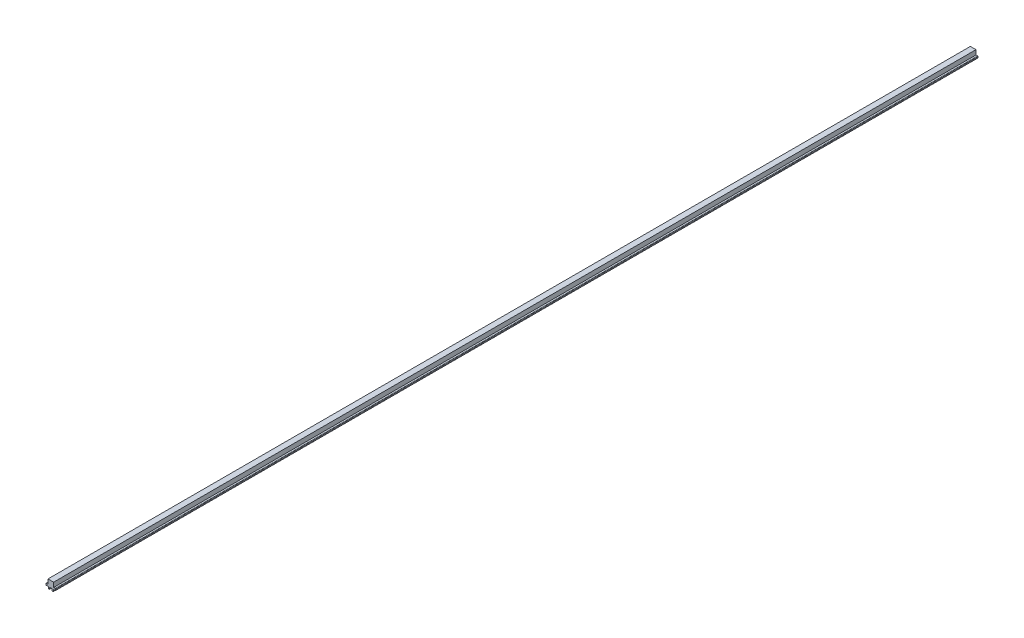
SolidWorks part; units mm, degrees
ref_plane "Front Plane" through (0, 0, 0) normal (0, 0, 1) x (1, 0, 0)
ref_plane "Top Plane" through (0, 0, 0) normal (0, 1, 0) x (1, 0, 0)
ref_plane "Right Plane" through (0, 0, 0) normal (1, 0, 0) x (0, 0, -1)
sketch "Sketch2" plane through (0, 0, 0) normal (0, 0, 1) x (1, 0, 0)
  line L0 (-1.4166, 5.1268) -> (-1.4166, -5.0982) construction
  line L1 (-4.4666, 5.1268) -> (1.6334, 5.1268)
  line L2 (-4.4666, 5.1268) -> (-4.4666, 2.8768)
  line L3 (-4.4666, 2.8768) -> (1.6334, 2.8768)
  line L4 (1.6334, 5.1268) -> (1.6334, 2.8768)
  line L5 (-4.4666, 2.8768) -> (1.6334, 2.8768)
  line L6 (-4.4666, 2.8768) -> (-4.4666, -1.8732)
  line L7 (-4.4666, -1.8732) -> (1.6334, -1.8732)
  line L8 (1.6334, 2.8768) -> (1.6334, -1.8732)
  line L9 (1.6334, 0.1268) -> (3.8334, 0.1268)
  line L10 (1.6334, 0.1268) -> (1.6334, -1.8732)
  line L11 (1.6334, -1.8732) -> (3.8334, -1.8732)
  line L12 (3.8334, 0.1268) -> (3.8334, -1.8732)
  line L13 (-4.4666, -1.8732) -> (-6.6666, -1.8732)
  line L14 (-0.1166, -1.8732) -> (1.3834, -1.8732)
  line L15 (-0.1166, -1.8732) -> (-0.1166, -4.0732)
  line L16 (-0.1166, -4.0732) -> (1.3834, -4.0732)
  line L17 (1.3834, -1.8732) -> (1.3834, -4.0732)
  line L18 (-6.6666, 0.1268) -> (-6.6666, -1.8732)
  line L19 (-4.4666, 0.1268) -> (-6.6666, 0.1268)
  line L20 (-4.4666, 0.1268) -> (-4.4666, -1.8732)
  line L21 (-2.7166, -4.0732) -> (-4.2166, -4.0732)
  line L22 (-4.2166, -1.8732) -> (-4.2166, -4.0732)
  line L23 (-2.7166, -1.8732) -> (-4.2166, -1.8732)
  line L24 (-2.7166, -1.8732) -> (-2.7166, -4.0732)
  dimension "D1" = 6.1
  dimension "D2" = 2.25
  dimension "D3" = 4.75
  dimension "D4" = 2.2
  dimension "D5" = 2
  dimension "D6" = 1.3
  dimension "D7" = 2.2
  dimension "D8" = 1.5
  dimension "D9" = 4.4666
extrude "Boss-Extrude1" add sketch "Sketch2" along normal blind 1000 contours L1 L0 L5 L4 | L0 L3 L6 L7 | L5 L0 L7 L8 | L0 L1 L2 L3 | L12 L9 L8 L11 | L17 L7 L15 L16 | L24 L7 L22 L21 | L6 L19 L18 L13 region at (0.1084, 4.0018, 0) region at (-2.9416, 4.0018, 0) region at (0.1084, 0.5018, 0) region at (-2.9416, 0.5018, 0) region at (-3.4666, -2.9732, 0) region at (0.6334, -2.9732, 0) region at (-5.5666, -0.8732, 0) region at (2.7334, -0.8732, 0)
fillet "Fillet1" radius 0.5 4 edges at (3.8334, -1.8732, 500) (3.8334, 0.1268, 500) (-6.6666, -1.8732, 500) (-6.6666, 0.1268, 500)
fillet "Fillet2" radius 0.5 4 edges at (1.3834, -4.0732, 500) (-0.1166, -4.0732, 500) (-4.2166, -4.0732, 500) (-2.7166, -4.0732, 500)
